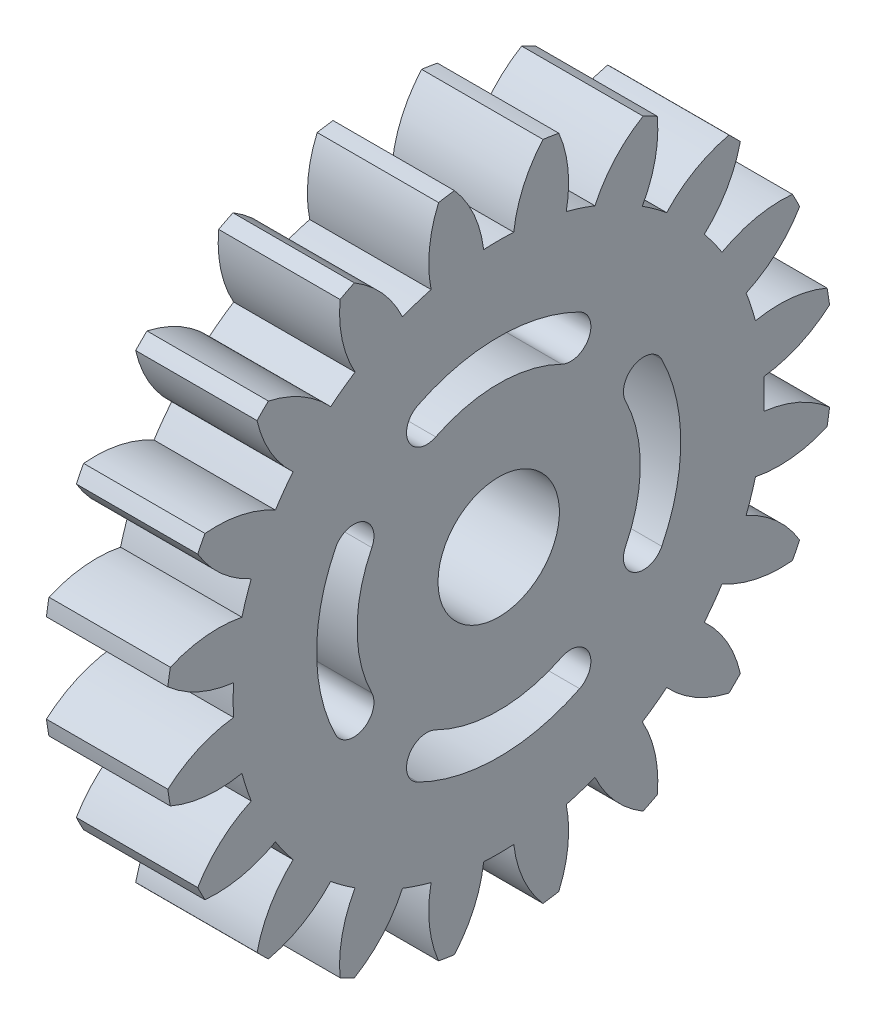
SolidWorks part; units mm, degrees
ref_plane "Plane1" through (0, 0, 0) normal (0, 0, 1) x (1, 0, 0)
ref_plane "Plane2" through (0, 0, 0) normal (0, 1, 0) x (1, 0, 0)
ref_plane "Plane3" through (0, 0, 0) normal (1, 0, 0) x (0, 0, -1)
sketch "HoldingSke" plane through (0, 0, 0) normal (0, 1, 0) x (1, 0, 0)
  line L0 (0, 0) -> (0.6265, -0.228)
  line L1 (-15, 0) -> (100, 0) construction
  line L2 (0, 0) -> (-2.1039, 2.3779)
  line L3 (0, 0) -> (-11.863, 4.5341)
  line L4 (0, 0) -> (8.1152, 2.9537)
  line L5 (0, 0) -> (-46.8476, -17.4728)
  line L6 (0, 0) -> (-4.9738, -3.3558)
  line L7 (-2.1039, 2.3779) -> (8.6586, 51.2059)
  line L8 (-76.2, 54.61) -> (-75.2, 54.61)
  line L9 (-71.009, 38.7566) -> (-53.1078, 45.2721)
  line L10 (-76.2, 71.12) -> (104.1128, 71.12)
  line L11 (0, 0) -> (-6, 0)
  line L12 (-76.2, 101.6) -> (-76.147, 101.6)
  line L13 (24.9733, 27.94) -> (52.9518, 28.4284)
  line L14 (24.9733, 27.94) -> (24.9743, 27.94)
  line L15 (24.9733, 27.94) -> (100.4006, 29.5858)
  line L16 (-63.627, -1.5) -> (-12.827, -1.5)
  circle A0 centre (0, 0) radius 3
  circle A1 centre (0, 0) radius 13.124
  circle A2 centre (0, 0) radius 37.5
  circle A3 centre (0, 0) radius 3
  dimension "Num_teeth" = 20
  dimension "Pitch_radius" = 180.3128
  dimension "Width" = 6
  dimension "Thickness" = 6
sketch "BasProSke" plane through (0, 0, 0) normal (0, 1, 0) x (1, 0, 0)
  line L0 (-10, 0) -> (60, 0) construction
  line L1 (0, 0) -> (0, 16.5)
  line L2 (0, 0) -> (6, 0)
  line L3 (6, 0) -> (6, 16.5)
  line L4 (6, 16.5) -> (0, 16.5)
  dimension "Thickness" = 6
  dimension "Diameter" = 33
revolve "Base-Revolve" add sketch "BasProSke" angle 360 about L0
sketch "TooCutSke" plane through (0, 0, 0) normal (1, 0, 0) x (0, 0, -1)
  line L1 (0, 0) -> (0, 107) construction
  line L2 (0, 0) -> (-1.2696, 14.9462) construction
  line L3 (0, 0) -> (-4.6808, 29.5532) construction
  line L4 (-1.2696, 14.9462) -> (-2.3404, 14.7766) construction
  arc A0 (0.7438, 13.1029) -> (-0.7438, 13.1029) centre (0, 0) ccw
  arc A1 (2.21, 16.377) -> (-2.21, 16.377) centre (0, 0) ccw
  circle A2 centre (0, 0) radius 15 construction
  circle A3 centre (0, 0) radius 14.0954 construction
  arc A4 (-0.7438, 13.1029) -> (-2.21, 16.377) centre (-6.7025, 12.3999) ccw
  arc A5 (2.21, 16.377) -> (0.7438, 13.1029) centre (6.7025, 12.3999) ccw
extrude "ToothCut" cut sketch "TooCutSke" along normal through all
fillet "Breaks" [suppressed] radius 0.03 tangent propagation no
fillet "RootFillets" [suppressed] radius 0.376
pattern_circular "TeethCuts" count 20 every 18 about axis through (-10, 0, 0) along (1, 0, 0) of "ToothCut", "RootFillets", "Breaks"
sketch "HubNeaOneSke" plane through (0, 0, 0) normal (-1, 0, 0) x (0, 0, 1)
  circle A0 centre (0, 0) radius 13.124
  dimension "Diameter" = 26.248
extrude "HubNearOne" [suppressed] add sketch "HubNeaOneSke" along normal blind 44.0001
sketch "HubNeaBotSke" plane through (0, 0, 0) normal (-1, 0, 0) x (0, 0, 1)
  circle A0 centre (0, 0) radius 13.124
  dimension "Diameter" = 26.248
extrude "HubNearBoth" [suppressed] add sketch "HubNeaBotSke" along normal blind 22
ref_plane "FarPln" through (6, 0, 0) normal (1, 0, 0) x (0, 0, -1)
sketch "HubFarSke" plane through (6, 0, 0) normal (1, 0, 0) x (0, 0, -1)
  circle A0 centre (0, 0) radius 13.124
  dimension "Diameter" = 26.248
extrude "HubFar" [suppressed] add sketch "HubFarSke" along normal blind 22
sketch "BorSke" plane through (0, 0, 0) normal (1, 0, 0) x (0, 0, -1)
  circle A0 centre (0, 0) radius 3
  dimension "Diameter" = 6
extrude "Bore" cut sketch "BorSke" along normal mid plane 100.0001
sketch "KeySke" plane through (0, 0, 0) normal (1, 0, 0) x (0, 0, -1)
  line L0 (-1, 0) -> (-1, 4)
  line L1 (-1, 4) -> (1, 4)
  line L2 (1, 4) -> (1, 0)
  line L3 (0, 0) -> (0, 34) construction
  line L4 (-1, 0) -> (1, 0)
  dimension "Width" = 2
extrude "Keyway" [suppressed] cut sketch "KeySke" along normal mid plane 100.0001
pattern_circular "Keyway2" [suppressed] count 2 every 90 about axis through (-10, 0, 0) along (1, 0, 0) reverse direction yes
sketch "Sketch1" plane through (6, 0, 0) normal (1, 0, 0) x (0, 0, -1)
  line L0 (4, 8.0623) -> (3.1111, 6.2706) construction
  line L1 (0, 0) -> (0, 14.2294) construction
  arc A0 (0, 9) -> (4, 8.0623) centre (0, 0) cw
  arc A1 (0, 7) -> (3.1111, 6.2706) centre (0, 0) cw
  circle A2 centre (3.5556, 7.1665) radius 1
  arc A3 (0, 7) -> (-3.1111, 6.2706) centre (0, 0) ccw
  arc A4 (0, 9) -> (-4, 8.0623) centre (0, 0) ccw
  circle A5 centre (-3.5556, 7.1665) radius 1
  dimension "D1" = 9
  dimension "D3" = 4
  dimension "D2" = 2
extrude "Cut-Extrude1" cut sketch "Sketch1" against normal blind 10 contours A4 A5 A3 A1 A2 A0 | A5 | A2 region at (6, 7.8702, 0) region at (6, 7.1665, -3.5556) region at (6, 7.1665, 3.5556)
pattern_circular "CirPattern1" count 4 over 360 about axis through (6, 0, 0) along (1, 0, 0) of "Cut-Extrude1"
equation "' \"Module@HoldingSke\" = 6.35"
equation "' \"Num_teeth@HoldingSke\" = 12"
equation "' \"Ap@HoldingSke\" =  20"
equation "' \"Ap@HoldingSke\" = 20"
equation "' \"Width@HoldingSke\" = 0.5 * 25.4"
equation "' \"Hub_dia@HoldingSke\"= 1 * 25.4"
equation "' \"Hub_dia@HoldingSke\" = 1 * 25.4"
equation "' \"Overall_len@HoldingSke\" = 1.0 * 25.4"
equation "' \"Bore@HoldingSke\" = 0.75 * 25.4"
equation "' \"T_dim@HoldingSke\" = 0.1 * 25.4"
equation "' \"Width@KeySke\" = 0.25 * 25.4"
equation "' \"Show_teeth@HoldingSke\" = 13"
equation "' \"Backlash@HoldingSke\" = 0.009 * 25.4"
equation "' \"Addendum_fac@HoldingSke\" = 1.0"
equation "' \"Dedendum_fac@HoldingSke\" = 1.25"
equation "' \"Dedendum_add@HoldingSke\" = 0.00005 * 25.4"
equation "' \"Clearance_fac@HoldingSke\" = 0.25"
equation "\"Pitch@HoldingSke\" = 1 / \"Module@HoldingSke\""
equation "\"Overcut_dia@TooCutSke\" = (\"Num_teeth@HoldingSke\" + 2 * \"Addendum_fac@HoldingSke\") / \"Pitch@HoldingSke\" + 0.002 * 25.4"
equation "\"Pitch_dia@TooCutSke\" = \"Num_teeth@HoldingSke\" / \"Pitch@HoldingSke\""
equation "\"Base_dia@TooCutSke\" = \"Num_teeth@HoldingSke\" / \"Pitch@HoldingSke\" * cos((\"Ap@HoldingSke\"  * 3.14159265 / 180))"
equation "\"Root_dia@TooCutSke\" = (\"Num_teeth@HoldingSke\" + 2) / \"Pitch@HoldingSke\" - 2 * (\"Addendum_fac@HoldingSke\" + \"Dedendum_fac@HoldingSke\") / \"Pitch@HoldingSke\" - \"Dedendum_add@HoldingSke\" * 2"
equation "\"Half_ang@TooCutSke\" = 180 / \"Num_teeth@HoldingSke\""
equation "\"Half_CT@TooCutSke\" = \"Num_teeth@HoldingSke\" / \"Pitch@HoldingSke\" * sin((3.14159265 / 2 / \"Num_teeth@HoldingSke\")) / 2 - 7 * \"Backlash@HoldingSke\" / 4"
equation "\"Flank_rad@TooCutSke\" = \"Num_teeth@HoldingSke\" / \"Pitch@HoldingSke\" / 5"
equation "\"Radius@RootFillets\" = \"Clearance_fac@HoldingSke\" / \"Pitch@HoldingSke\" + \"Dedendum_add@HoldingSke\""
equation "\"Break_rad@Breaks\" = 0.02 / \"Pitch@HoldingSke\""
equation "\"Thickness@HoldingSke\" = \"Width@HoldingSke\""
equation "\"OAL@HoldingSke\" = \"Thickness@HoldingSke\""
equation "\"MHD@HoldingSke\" = (\"Num_teeth@HoldingSke\" + 2) / \"Pitch@HoldingSke\" - 2 * (\"Addendum_fac@HoldingSke\" + \"Dedendum_fac@HoldingSke\")  / \"Pitch@HoldingSke\" - \"Dedendum_add@HoldingSke\" * 2"
equation "\"MBD@HoldingSke\" = (\"Num_teeth@HoldingSke\" + 2) / \"Pitch@HoldingSke\" - 2 * (\"Addendum_fac@HoldingSke\" + \"Dedendum_fac@HoldingSke\")  / \"Pitch@HoldingSke\" - \"Dedendum_add@HoldingSke\" * 2 - 0.002 * 25.4"
equation "\"MHD@HoldingSke\" = ((sgn( \"MHD@HoldingSke\" - \"Hub_dia@HoldingSke\" )-1)*( \"MHD@HoldingSke\" - \"Hub_dia@HoldingSke\" ))/-2+ \"Hub_dia@HoldingSke\""
equation "\"MBD@HoldingSke\" = ((sgn( \"MBD@HoldingSke\" - \"Bore@HoldingSke\" )-1)*( \"MBD@HoldingSke\" - \"Bore@HoldingSke\" ))/-2+ \"Bore@HoldingSke\""
equation "\"OAL@HoldingSke\" = ((sgn( \"OAL@HoldingSke\" - \"Overall_len@HoldingSke\" )+1)*( \"OAL@HoldingSke\" - \"Overall_len@HoldingSke\" ))/2 + \"Overall_len@HoldingSke\" + 0.000002 * 25.4"
equation "\"Num_teeth@TeethCuts\" = int( \"Show_teeth@HoldingSke\" ) + 1"
equation "\"Num_teeth@TeethCuts\" = ((sgn( \"Num_teeth@TeethCuts\" - \"Num_teeth@HoldingSke\" )-1)*( \"Num_teeth@TeethCuts\" - \"Num_teeth@HoldingSke\" ))/-2+ \"Num_teeth@HoldingSke\""
equation "\"Num_teeth@TeethCuts\" = ((sgn( \"Num_teeth@TeethCuts\" - 2.0)+1)*( \"Num_teeth@TeethCuts\" - 2.0))/2 +2.0"
equation "\"Angle@TeethCuts\" = 360.0 / \"Num_teeth@HoldingSke\""
equation "\"Diameter@BasProSke\" = (\"Num_teeth@HoldingSke\" + 2 * \"Addendum_fac@HoldingSke\") / \"Pitch@HoldingSke\""
equation "\"Thickness@BasProSke\"  = \"Thickness@HoldingSke\""
equation "' \"Fillet_rad@BasProSke\" =  \"Thickness@HoldingSke\" * 0.05"
equation "' \"Fillet_rad@BasProSke\" = \"Thickness@HoldingSke\" * 0.05"
equation "\"MHD@HoldingSke\" = ((sgn( \"MHD@HoldingSke\" - \"Root_dia@TooCutSke\" )-1)*( \"MHD@HoldingSke\" - \"Root_dia@TooCutSke\" ))/-2+ \"Root_dia@TooCutSke\""
equation "\"Diameter@HubNeaOneSke\" = \"MHD@HoldingSke\""
equation "\"Length@HubNearOne\" = \"OAL@HoldingSke\" - \"Thickness@BasProSke\""
equation "\"Diameter@HubNeaBotSke\" = \"MHD@HoldingSke\""
equation "\"Length@HubNearBoth\" = ( \"OAL@HoldingSke\" - \"Thickness@BasProSke\" ) / 2.0"
equation "\"Thickness@FarPln\" = \"Thickness@BasProSke\""
equation "\"Diameter@HubFarSke\" = \"MHD@HoldingSke\""
equation "\"Length@HubFar\" = ( \"OAL@HoldingSke\" - \"Thickness@BasProSke\" ) / 2.0"
equation "\"Diameter@BorSke\" = \"MBD@HoldingSke\""
equation "\"D1@Bore\" = \"OAL@HoldingSke\" * 2.0"
equation "\"D1@Keyway\" = \"OAL@HoldingSke\" * 2.0"
equation "\"Offset@KeySke\" = \"T_dim@HoldingSke\" + \"MBD@HoldingSke\" / 2.0"
